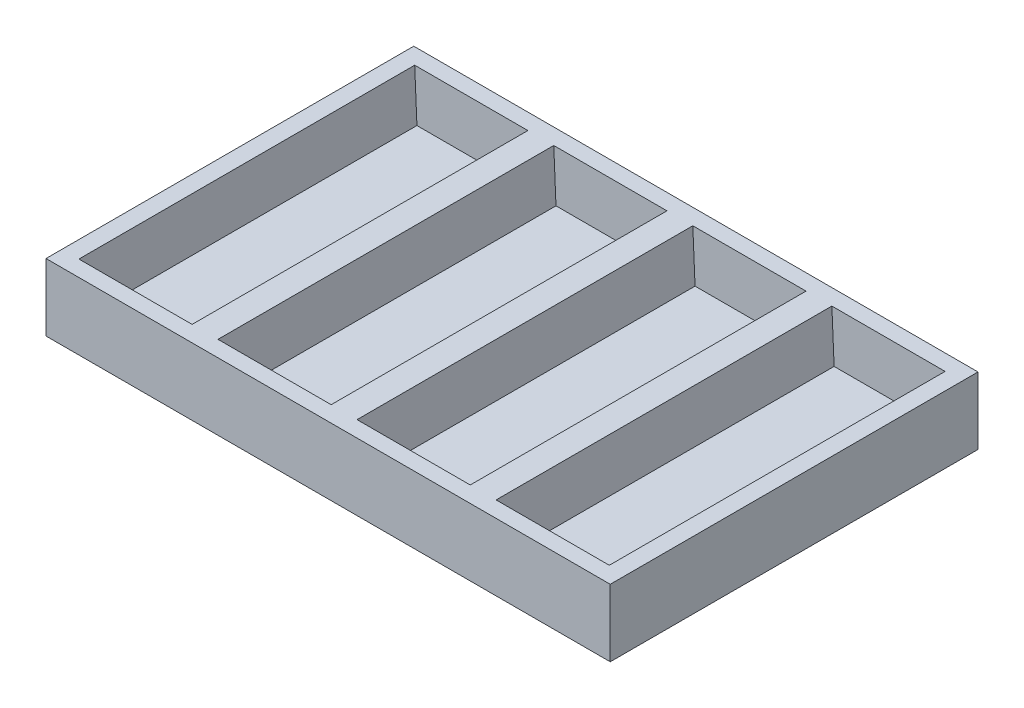
SolidWorks part; units mm, degrees
ref_plane "Front Plane" through (0, 0, 0) normal (0, 0, 1) x (1, 0, 0)
ref_plane "Top Plane" through (0, 0, 0) normal (0, 1, 0) x (1, 0, 0)
ref_plane "Right Plane" through (0, 0, 0) normal (1, 0, 0) x (0, 0, -1)
sketch "Sketch1" plane through (0, 0, 0) normal (0, 0, 1) x (1, 0, 0)
  line L0 (0, 0) -> (0, 107.95)
  line L1 (0, 0) -> (224.0826, 0) construction
  line L2 (0, 0) -> (0, 107.95) construction
  line L3 (0, 107.95) -> (224.0826, 107.95) construction
  line L4 (7.611, 6.35) -> (7.611, 107.95) construction
  line L5 (0, 107.95) -> (3.175, 107.95)
  line L6 (3.175, 107.95) -> (7.611, 6.35)
  line L7 (7.611, 6.35) -> (50.791, 6.35)
  line L8 (50.791, 6.35) -> (55.2269, 107.95)
  line L9 (55.2269, 107.95) -> (55.2269, 0) construction
  line L10 (55.2269, 107.95) -> (58.4019, 107.95)
  line L11 (58.4019, 107.95) -> (58.4019, 0) construction
  line L12 (7.611, 107.95) -> (3.175, 107.95) construction
  line L13 (58.4019, 107.95) -> (62.8379, 6.35)
  line L14 (62.8379, 6.35) -> (106.0179, 6.35)
  line L15 (106.0179, 6.35) -> (110.4538, 107.95)
  line L16 (110.4538, 107.95) -> (113.6288, 107.95)
  line L17 (113.6288, 107.95) -> (118.0648, 6.35)
  line L18 (118.0648, 6.35) -> (161.2448, 6.35)
  line L19 (161.2448, 6.35) -> (165.6807, 107.95)
  line L20 (165.6807, 107.95) -> (168.8557, 107.95)
  line L21 (168.8557, 107.95) -> (173.2917, 6.35)
  line L22 (173.2917, 6.35) -> (216.4717, 6.35)
  line L23 (216.4717, 6.35) -> (220.9076, 107.95)
  line L24 (220.9076, 107.95) -> (224.0826, 107.95)
  line L25 (224.0826, 107.95) -> (224.0826, 0)
  line L26 (224.0826, 0) -> (0, 0)
  line L27 (110.4538, 107.95) -> (110.4538, 0) construction
  line L28 (113.6288, 107.95) -> (113.6288, 0) construction
  line L29 (165.6807, 107.95) -> (165.6807, 0) construction
  line L30 (168.8557, 107.95) -> (168.8557, 0) construction
  line L31 (50.791, 6.35) -> (62.8379, 6.35) construction
  line L32 (106.0179, 6.35) -> (118.0648, 6.35) construction
  line L33 (161.2448, 6.35) -> (173.2917, 6.35) construction
  line L34 (112.0413, 113.03) -> (112.0413, -30.1165) construction
  line L35 (-40.3587, 141.2445) -> (-40.3587, -34.167) construction
  line L36 (264.4413, 143.4606) -> (264.4413, -34.167) construction
  line L37 (50.791, 6.35) -> (50.791, 113.03) construction
  line L38 (92.9913, 151.13) -> (131.0913, 151.13) construction
  line L39 (92.9913, 151.13) -> (92.9913, 113.03) construction
  line L40 (92.9913, 113.03) -> (131.0913, 113.03) construction
  line L41 (131.0913, 151.13) -> (131.0913, 113.03) construction
  line L42 (12.691, 113.03) -> (50.791, 113.03) construction
  line L43 (12.691, 113.03) -> (12.691, 151.13) construction
  line L44 (12.691, 151.13) -> (50.791, 151.13) construction
  line L45 (50.791, 113.03) -> (50.791, 151.13) construction
  line L46 (71.8911, 162.5443) -> (71.8911, 143.1127) construction
  point P38 (112.0413, 113.03)
  point P43 (50.791, 113.03)
  point P45 (31.741, 151.13)
  point P46 (112.0413, 151.13)
  dimension "D1" = 52.0519
  dimension "D2" = 107.95
  dimension "D3" = 43.18
  dimension "D4" = 6.35
  dimension "D5" = 2.5
  dimension "D6" = 2.5
  dimension "D7" = 3.175
  dimension "D8" = 3.175
  dimension "D9" = 4.436
  dimension "D10" = 3.175
  dimension "D11" = 3.175
  dimension "D12" = 3.175
  dimension "D13" = 2.5
  dimension "D14" = 2.5
  dimension "D15" = 2.5
  dimension "D16" = 2.5
  dimension "D17" = 2.5
  dimension "D18" = 2.5
  dimension "D19" = 43.18
  dimension "D20" = 43.18
  dimension "D21" = 43.18
  dimension "D22" = 224.0826
  dimension "D23" = 112.0413
  dimension "D24" = 304.8
  dimension "D25" = 40.3587
  dimension "D26" = 40.3587
  dimension "D27" = 38.1
  dimension "D28" = 38.1
  dimension "D29" = 38.1
  dimension "D30" = 38.1
  dimension "D31" = 5.08
  dimension "D32" = 80.3004
  dimension "D33" = 40.1502
extrude "Boss-Extrude1" add sketch "Sketch1" along normal blind 146.05
sketch "Sketch2" plane through (0, 0, 146.05) normal (0, 0, 1) x (1, 0, 0)
  line L0 (3.175, 107.95) -> (55.2269, 107.95)
  line L1 (55.2269, 107.95) -> (50.791, 6.35)
  line L2 (50.791, 6.35) -> (7.611, 6.35)
  line L3 (7.611, 6.35) -> (3.175, 107.95)
  line L4 (58.4019, 107.95) -> (62.8379, 6.35)
  line L5 (62.8379, 6.35) -> (106.0179, 6.35)
  line L6 (106.0179, 6.35) -> (110.4538, 107.95)
  line L7 (110.4538, 107.95) -> (58.4019, 107.95)
  line L8 (113.6288, 107.95) -> (118.0648, 6.35)
  line L9 (118.0648, 6.35) -> (161.2448, 6.35)
  line L10 (161.2448, 6.35) -> (165.6807, 107.95)
  line L11 (165.6807, 107.95) -> (113.6288, 107.95)
  line L12 (168.8557, 107.95) -> (173.2917, 6.35)
  line L13 (173.2917, 6.35) -> (216.4717, 6.35)
  line L14 (216.4717, 6.35) -> (220.9076, 107.95)
  line L15 (220.9076, 107.95) -> (168.8557, 107.95)
extrude "Boss-Extrude2" add sketch "Sketch2" against normal blind 6.35
ref_plane "Plane1" through (0, 0, 73.025) normal (0, 0, -1) x (-1, 0, 0)
mirror "Mirror1" about plane through (0, 0, 73.025) normal (0, 0, -1) of "Boss-Extrude2"
ref_plane "Plane2" through (112.0413, 0, 0) normal (1, 0, 0) x (0, 0, -1)
sketch "Sketch3" plane through (0, 107.95, 0) normal (0, 1, 0) x (1, 0, 0)
  line L1 (-24.2108, -174.0169) -> (250.1805, -174.0169)
  line L2 (-24.2108, -174.0169) -> (-24.2108, 38.1413)
  line L3 (-24.2108, 38.1413) -> (250.1805, 38.1413)
  line L4 (250.1805, -174.0169) -> (250.1805, 38.1413)
extrude "Cut-Extrude1" cut sketch "Sketch3" against normal offset from surface (81.28 mm away) 20.32 up to face at (84.4279, 6.35, 73.025)
equation "\"D8@Sketch1\"=\"D7@Sketch1\""
equation "\"D10@Sketch1\"=\"D8@Sketch1\""
equation "\"D11@Sketch1\"=\"D7@Sketch1\""
equation "\"D12@Sketch1\"=\"D7@Sketch1\""
equation "\"D13@Sketch1\"=\"D5@Sketch1\""
equation "\"D6@Sketch1\"=\"D5@Sketch1\""
equation "\"D14@Sketch1\"=\"D5@Sketch1\""
equation "\"D15@Sketch1\"=\"D5@Sketch1\""
equation "\"D16@Sketch1\"=\"D5@Sketch1\""
equation "\"D17@Sketch1\"=\"D5@Sketch1\""
equation "\"D18@Sketch1\"=\"D5@Sketch1\""
equation "\"D19@Sketch1\"=\"D3@Sketch1\""
equation "\"D20@Sketch1\"=\"D3@Sketch1\""
equation "\"D21@Sketch1\"=\"D3@Sketch1\""
equation "\"D23@Sketch1\"=\"D22@Sketch1\"/2"
equation "\"D25@Sketch1\"=(\"D24@Sketch1\"-\"D22@Sketch1\")/2"
equation "\"D33@Sketch1\"=\"D32@Sketch1\"/2"
